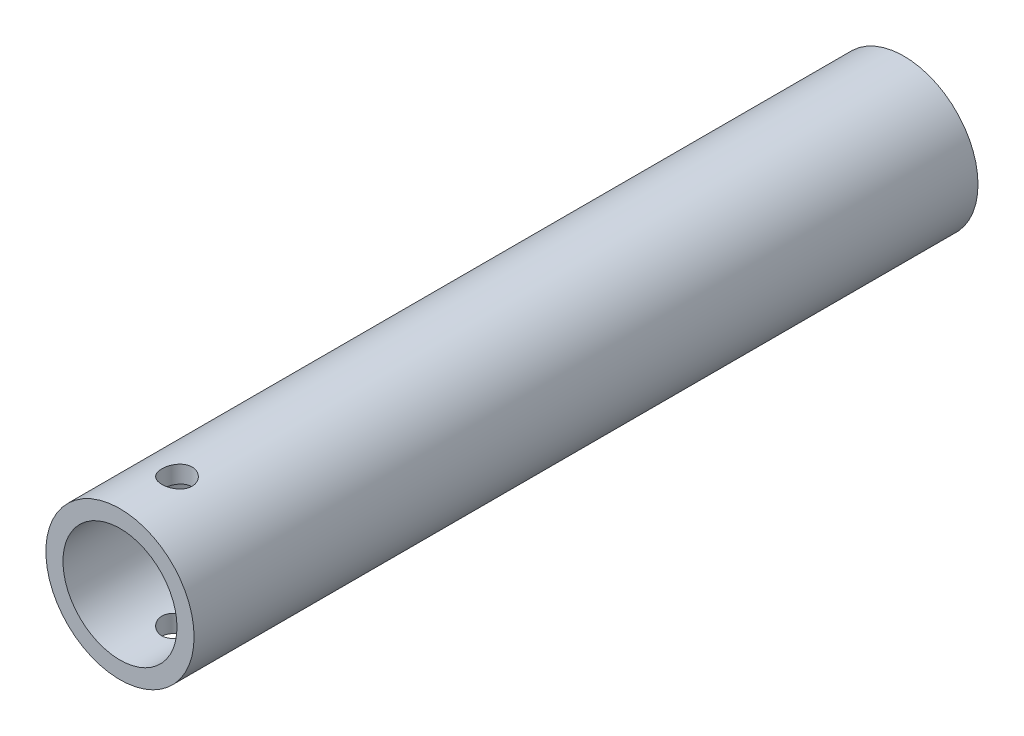
SolidWorks part; units mm, degrees
ref_plane "Front Plane" through (0, 0, 0) normal (0, 0, 1) x (1, 0, 0)
ref_plane "Top Plane" through (0, 0, 0) normal (0, 1, 0) x (1, 0, 0)
ref_plane "Right Plane" through (0, 0, 0) normal (1, 0, 0) x (0, 0, -1)
sketch "Sketch1" plane through (0, 0, 0) normal (0, 0, 1) x (1, 0, 0)
  circle A0 centre (0, 0) radius 13
  circle A1 centre (0, 0) radius 10
  dimension "D1" = 26
  dimension "D2" = 3
extrude "Boss-Extrude1" add sketch "Sketch1" along normal blind 137.5
sketch "Sketch3" plane through (0, 0, 0) normal (0, 1, 0) x (1, 0, 0)
  line L0 (0, 5.5211) -> (0, -37.2706) construction
  line L1 (13, 0) -> (-13, 0) construction
  circle A0 centre (0, -10) radius 2.5
  circle A1 centre (0, -20) radius 2.5
  dimension "D1" = 5
  dimension "D2" = 10
  dimension "D3" = 20
extrude "Cut-Extrude1" cut sketch "Sketch3" against normal through all
sketch "Sketch4" plane through (0, 0, 0) normal (0, 1, 0) x (0, 0, -1)
  line L0 (-137.5, 0) -> (-119.9134, 0) construction
  line L1 (-137.5, 13) -> (-137.5, -13) construction
  circle A0 centre (-127.5, 0) radius 2.65
  dimension "D1" = 5.3
  dimension "D2" = 10
extrude "Cut-Extrude2" cut sketch "Sketch4" against normal through all and the other way blind 150
